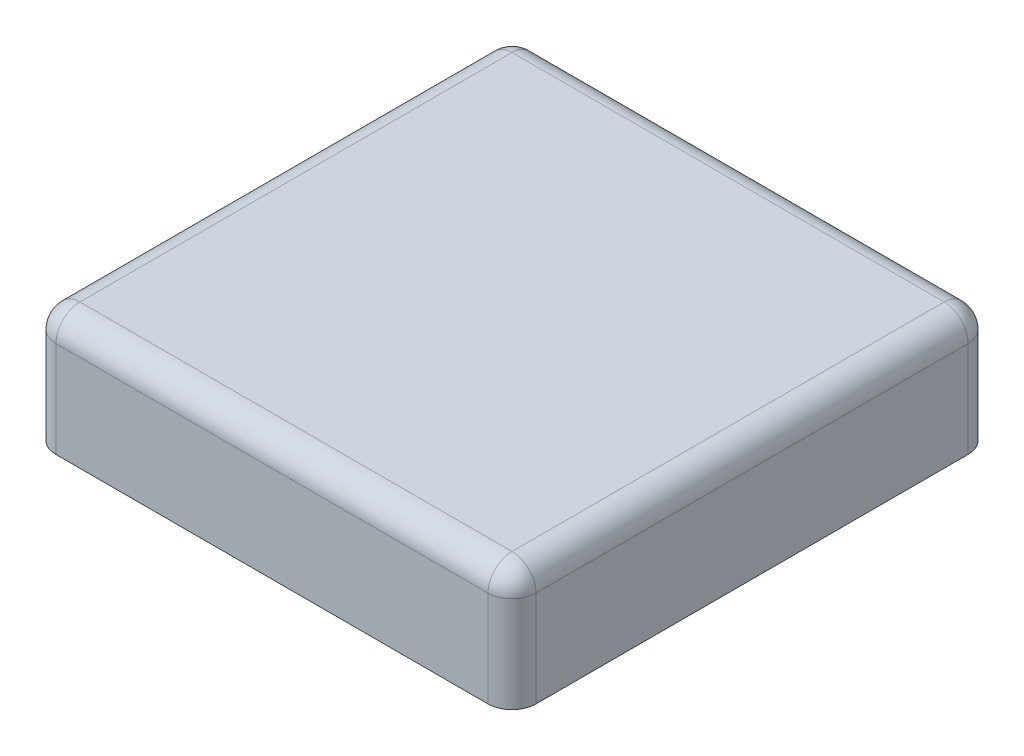
SolidWorks part; units mm, degrees
ref_plane "Front Plane" through (0, 0, 0) normal (0, 0, 1) x (1, 0, 0)
ref_plane "Top Plane" through (0, 0, 0) normal (0, 1, 0) x (1, 0, 0)
ref_plane "Right Plane" through (0, 0, 0) normal (1, 0, 0) x (0, 0, -1)
sketch "Sketch1" plane through (0, 0, 0) normal (0, 1, 0) x (1, 0, 0)
  line L1 (30, 30) -> (-30, 30)
  line L2 (30, 30) -> (30, -30)
  line L3 (30, -30) -> (-30, -30)
  line L4 (-30, 30) -> (-30, -30)
  line L5 (30, 30) -> (-30, -30) construction
  line L6 (30, -30) -> (-30, 30) construction
  point P0 (0, 0)
  dimension "D1" = 60
  dimension "D2" = 60
extrude "Boss-Extrude1" add sketch "Sketch1" along normal blind 15
fillet "Fillet1" radius 3 8 edges at (0, 15, -30) (30, 15, 0) (0, 15, 30) (-30, 15, 0) (-30, 7.5, 30) (-30, 7.5, -30) (30, 7.5, -30) (30, 7.5, 30)
shell "Shell1" thickness 3 removed face at (0, 0, 0)
